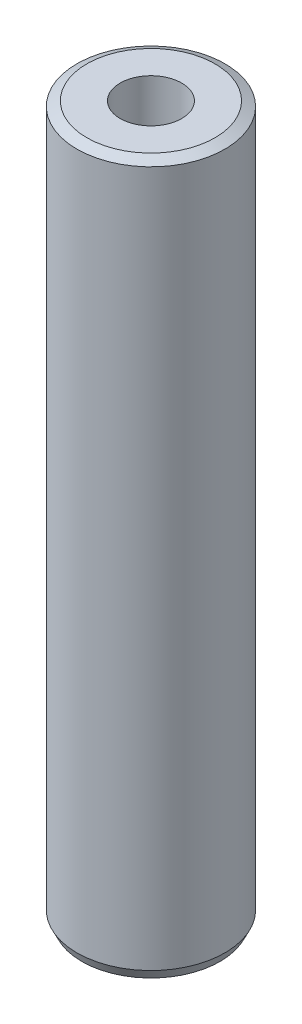
SolidWorks part; units mm, degrees
ref_plane "Front Plane" through (0, 0, 0) normal (0, 0, 1) x (1, 0, 0)
ref_plane "Top Plane" through (0, 0, 0) normal (0, 1, 0) x (1, 0, 0)
ref_plane "Right Plane" through (0, 0, 0) normal (1, 0, 0) x (0, 0, -1)
sketch "Sketch1" plane through (0, 0, 0) normal (0, 1, 0) x (1, 0, 0)
  circle A0 centre (0, 0) radius 45
  dimension "SHAFT_OD" = 90
extrude "Boss-Extrude1" add sketch "Sketch1" along normal blind 432.1855
sketch "Sketch2" plane through (0, 0, 0) normal (0, 1, 0) x (1, 0, 0)
  circle A0 centre (0, 0) radius 18.7113
  dimension "BORE_D" = 37.4226
extrude "Cut-Extrude1" cut sketch "Sketch2" along normal through all
chamfer "Chamfer1" distance 2.97 angle 63.822 2 edges at (0, 432.1855, 45) (0, 0, 45) first distance on face at (0, 432.1855, 45) first distance on face at (0, 0, 18.7113)
